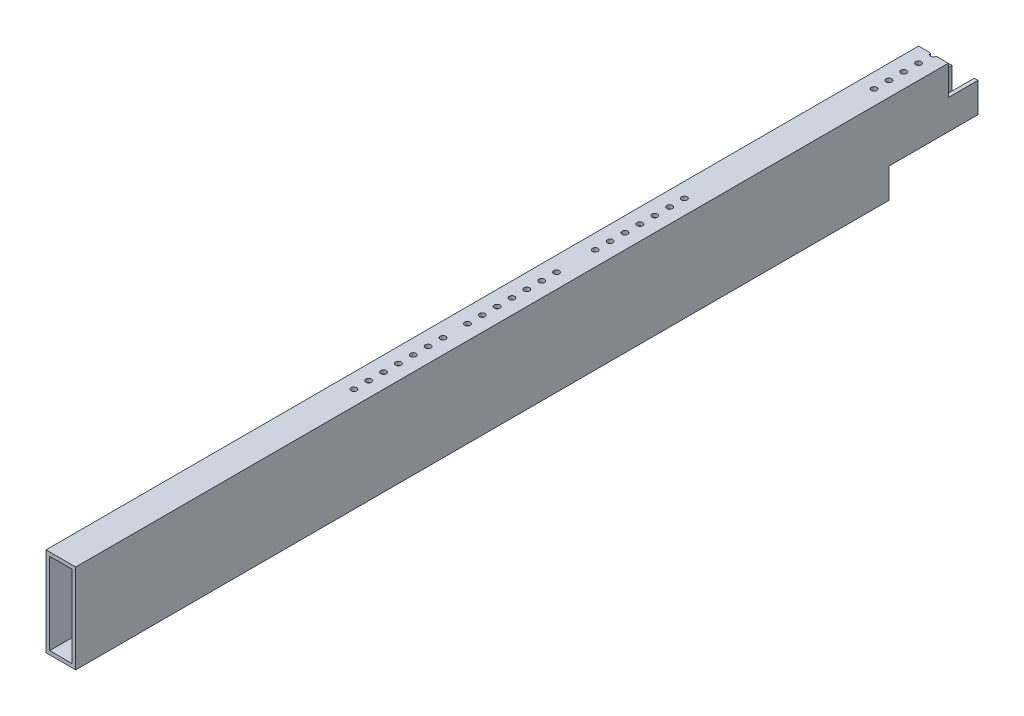
SolidWorks part; units mm, degrees
ref_plane "Front Plane" through (0, 0, 0) normal (0, 0, 1) x (1, 0, 0)
ref_plane "Top Plane" through (0, 0, 0) normal (0, 1, 0) x (1, 0, 0)
ref_plane "Right Plane" through (0, 0, 0) normal (1, 0, 0) x (0, 0, -1)
sketch "Sketch1" plane through (0, 0, 0) normal (0, 0, 1) x (1, 0, 0)
  line L1 (-12.7, -38.1) -> (12.7, -38.1)
  line L2 (-12.7, -38.1) -> (-12.7, 38.1)
  line L3 (-12.7, 38.1) -> (12.7, 38.1)
  line L4 (12.7, -38.1) -> (12.7, 38.1)
  line L5 (-12.7, -38.1) -> (12.7, 38.1) construction
  line L6 (-12.7, 38.1) -> (12.7, -38.1) construction
  point P0 (0, 0)
  dimension "D1" = 25.4
  dimension "D2" = 76.2
extrude "Boss-Extrude1" add sketch "Sketch1" along normal mid plane 771.398
shell "Shell1" thickness 3.175 removed face at (0, 0, -385.699) removed face at (0, 0, 385.699)
sketch "Sketch2" plane through (12.7, 0, 0) normal (1, 0, 0) x (0, 0, -1)
  line L1 (385.699, -38.1) -> (309.499, -38.1)
  line L2 (385.699, -38.1) -> (385.699, -12.7)
  line L3 (385.699, -12.7) -> (309.499, -12.7)
  line L4 (309.499, -38.1) -> (309.499, -12.7)
  dimension "D1" = 25.4
  dimension "D2" = 76.2
extrude "Cut-Extrude1" cut sketch "Sketch2" against normal through all
sketch "Sketch3" plane through (12.7, 0, 0) normal (1, 0, 0) x (0, 0, -1)
  line L1 (385.699, 38.1) -> (360.299, 38.1)
  line L2 (385.699, 38.1) -> (385.699, 12.7)
  line L3 (385.699, 12.7) -> (360.299, 12.7)
  line L4 (360.299, 38.1) -> (360.299, 12.7)
  dimension "D1" = 25.4
extrude "Cut-Extrude2" cut sketch "Sketch3" against normal through all
sketch "Sketch4" plane through (0, 38.1, 0) normal (0, 1, 0) x (1, 0, 0)
  line L0 (-12.7, 360.299) -> (12.7, 360.299) construction
  circle A0 centre (0, 147.3945) radius 2.3812
  circle A1 centre (0, 134.6945) radius 2.3812
  circle A2 centre (0, 121.9945) radius 2.3812
  circle A3 centre (0, 109.2945) radius 2.3812
  circle A4 centre (0, 96.5945) radius 2.3812
  circle A5 centre (0, 83.8945) radius 2.3812
  circle A6 centre (0, 71.1945) radius 2.3812
  circle A7 centre (0, 38.0987) radius 2.3812
  circle A8 centre (0, 25.3987) radius 2.3813
  circle A9 centre (0, 12.6987) radius 2.3813
  circle A10 centre (0, -0.0013) radius 2.3813
  circle A11 centre (0, -12.7013) radius 2.3812
  circle A12 centre (0, -25.4013) radius 2.3812
  circle A13 centre (0, -38.1013) radius 2.3812
  circle A15 centre (0, -58.9932) radius 2.3812
  circle A16 centre (0, -71.6932) radius 2.3812
  circle A17 centre (0, -84.3932) radius 2.3812
  circle A18 centre (0, -97.0932) radius 2.3812
  circle A19 centre (0, -109.7932) radius 2.3812
  circle A20 centre (0, -122.4932) radius 2.3812
  circle A21 centre (0, -135.1932) radius 2.3813
  point P33 (0, 360.299)
  dimension "D1" = 4.7625
  dimension "D3" = 12.7
  dimension "D4" = 12.7
  dimension "D5" = 12.7
  dimension "D6" = 12.7
  dimension "D7" = 12.7
  dimension "D8" = 12.7
  dimension "D9" = 322.2003
  dimension "D10" = 12.7
  dimension "D11" = 12.7
  dimension "D12" = 12.7
  dimension "D13" = 12.7
  dimension "D14" = 12.7
  dimension "D15" = 12.7
  dimension "D16" = 12.7
  dimension "D17" = 419.2922
  dimension "D18" = 12.7
  dimension "D19" = 12.7
  dimension "D20" = 12.7
  dimension "D21" = 12.7
  dimension "D22" = 12.7
  dimension "D2" = 212.9045
extrude "Cut-Extrude3" cut sketch "Sketch4" against normal through all
sketch "Sketch5" plane through (0, 38.1, 0) normal (0, 1, 0) x (1, 0, 0)
  line L0 (-12.7, 360.299) -> (12.7, 360.299) construction
  circle A0 centre (0, 360.299) radius 2.3813
  circle A1 centre (0, 347.599) radius 2.3813
  circle A2 centre (0, 334.899) radius 2.3813
  circle A3 centre (0, 322.199) radius 2.3813
  circle A4 centre (0, 309.499) radius 2.3813
  dimension "D1" = 4.7625
  dimension "D3" = 12.7
  dimension "D4" = 12.7
  dimension "D5" = 12.7
  dimension "D8" = 0
  dimension "D2" = 12.7
extrude "Cut-Extrude4" cut sketch "Sketch5" against normal up to next
sketch "Sketch6" plane through (0, -38.1, 0) normal (0, -1, 0) x (1, 0, 0)
  line L0 (-12.7, -309.499) -> (12.7, -309.499) construction
  circle A0 centre (0, -309.499) radius 2.3813
  circle A1 centre (0, -296.799) radius 2.3813
  circle A2 centre (0, -284.099) radius 2.3813
  circle A3 centre (0, -258.699) radius 2.3813
  circle A6 centre (0, -271.399) radius 2.3813
  dimension "D1" = 4.7625
  dimension "D2" = 12.7
  dimension "D3" = 12.7
  dimension "D4" = 12.7
  dimension "D5" = 12.7
  dimension "D6" = 0
extrude "Cut-Extrude5" cut sketch "Sketch6" against normal up to next
sketch3d "3DSketch1" [suppressed]
  line L0 (0, 34.925, -109.2945) -> (0, 38.1, -109.2945) construction
  line L1 (0, 34.925, 97.0932) -> (0, 38.1, 97.0932) construction
  point P0 (0, 38.1, -109.2945)
  point P1 (0, 0, 0)
  point P4 (0, 38.1, 97.0932)
